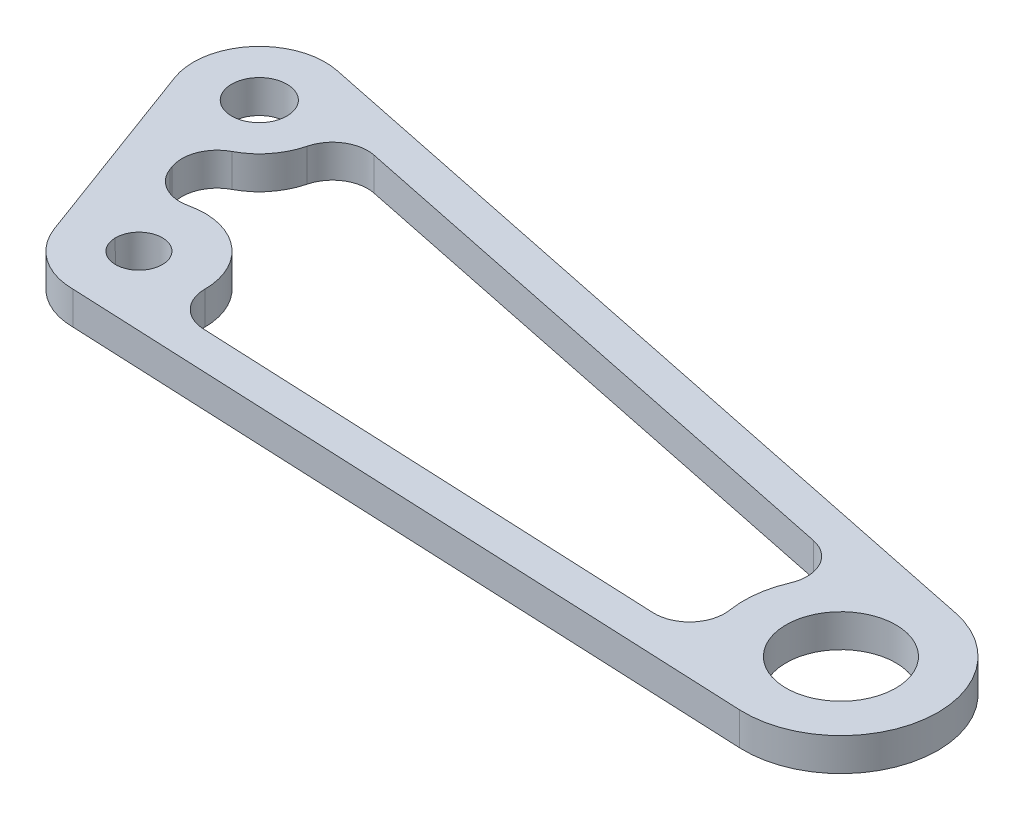
SolidWorks part; units mm, degrees
material "6061-T6 (SS)"
ref_plane "Front Plane" through (0, 0, 0) normal (0, 0, 1) x (1, 0, 0)
ref_plane "Top Plane" through (0, 0, 0) normal (0, 1, 0) x (1, 0, 0)
ref_plane "Right Plane" through (0, 0, 0) normal (1, 0, 0) x (0, 0, -1)
sketch "Sketch1" plane through (0, 0, 0) normal (0, 1, 0) x (1, 0, 0)
  line L0 (0, 0) -> (101.5644, 0) construction
  line L1 (101.5644, 0) -> (-10.2264, 27.6351) construction
  line L2 (-10.2264, 27.6351) -> (0, 0) construction
  line L3 (-23.321, 35.5752) -> (-8.933, -3.3057)
  line L8 (-8.3044, 36.9641) -> (104.3962, 13.7448)
  line L9 (0, -9.525) -> (100.9402, -14.0196)
  circle A0 centre (0, 0) radius 3.3782
  circle A1 centre (-10.2264, 27.6351) radius 4
  circle A2 centre (101.5644, 0) radius 7.9375
  arc A6 (154.4744, -3.2678) -> (153.7124, -9.525) centre (153.7124, -6.35) cw
  arc A8 (-19.5814, 39.7594) -> (-23.321, 35.5752) centre (-20.3433, 36.6771) ccw
  circle A9 centre (101.5644, 0) radius 14.0335
  circle A10 centre (0, 0) radius 9.525
  circle A11 centre (-10.2264, 27.6351) radius 9.525
  dimension "D4" = 15.875
  dimension "D5" = 8
  dimension "D6" = 9.525
  dimension "D9" = 6.7564
  dimension "D10" = 6.096
  dimension "D7" = 6.1468
  dimension "D8" = 5.525
  dimension "D2" = 29.4665
  dimension "D3" = 115.156
  dimension "D13" = 101.5644
extrude "Boss-Extrude2" add sketch "Sketch1" along normal blind 4.7625 contours A11 L3 A10 A9 | A10 A0 | A9 A2 | A11 A1 region at (40.933, 0, -8.4018) region at (-17.2469, 0, -33.6666) region at (-1.6316, 0, -9.1106) region at (112.1352, 0, -8.6149)
sketch "Sketch2" plane through (0, 4.7625, 0) normal (0, 1, 0) x (1, 0, 0)
  line L0 (-10.2264, 27.6351) -> (101.5644, 0)
  line L1 (101.5644, 0) -> (0, 0)
  line L2 (0, 0) -> (-10.2264, 27.6351)
  line L3 (-1.0786, 30.2887) -> (92.7872, 10.9499)
  line L4 (8.2235, -4.8061) -> (90.3707, -8.4639)
  line L5 (-16.3207, 34.9553) -> (0.139, -9.524)
  line L6 (-19.1594, 24.3294) -> (-8.933, -3.3057) construction
  line L7 (-8.3044, 36.9641) -> (104.3962, 13.7448) construction
  line L8 (0, -9.525) -> (100.9402, -14.0196) construction
  line L9 (-1.2935, 30.9407) -> (11.997, -4.9742)
  circle A0 centre (-10.2264, 27.6351) radius 9.525
  circle A1 centre (0, 0) radius 9.525
  circle A2 centre (101.5644, 0) radius 14.0335
  circle A4 centre (101.5644, 0) radius 7.9375 construction
  arc A5 (100.9402, -14.0196) -> (104.3962, 13.7448) centre (101.5644, 0) ccw construction
  arc A6 (-8.3044, 36.9641) -> (-19.1594, 24.3294) centre (-10.2264, 27.6351) ccw construction
  arc A7 (-8.933, -3.3057) -> (0, -9.525) centre (0, 0) ccw construction
  dimension "D1" = 6.35
  dimension "D2" = 5.08
  dimension "D3" = 5.08
extrude "Cut-Extrude1" cut sketch "Sketch2" against normal through all contours A2 L0 L9 A1 L1 | A2 L3 L9 L0 | A2 L1 A1 L4 | A1 L9 L0 A0 L2 | A0 L0 L9 L3 | A1 L1 L9 | A1 L4 L9 L1 | A1 L2 A0 L5 region at (-0.2166, 4.7625, -26.5844) region at (0.0572, 4.7625, -15.4252) region at (-6.627, 4.7625, -13.2574) region at (48.9758, 4.7625, -16.5434) region at (36.3839, 4.7625, -8.4441) region at (9.6562, 4.7625, -0.8369) region at (53.0895, 4.7625, 3.426) region at (10.1245, 4.7625, 3.0934)
fillet "Fillet1" radius 5.08 6 edges at (-10.0875, 2.3813, -18.1111) (-6.0943, 2.3813, -7.3202) (92.7872, 2.3813, -10.9499) (90.3707, 2.3813, 8.4639) (-1.0786, 2.3813, -30.2887) (8.2235, 2.3813, 4.8061)
ref_axis "Axis1" through (0, 4.7625, 0) along (0, -1, 0)
ref_plane "Plane1" through (0, 0, 0) normal (-0.0159, 0, -0.9999) x (0, -1, 0)
split line "Split Line1" [suppressed]
ref_point "Point2" [suppressed]
sketch "Sketch3" plane through (0, 0, 0) normal (-0.0159, 0, -0.9999) x (0, -1, 0)
  line L0 (-3.175, 28.2234) -> (-3.175, -33.0358)
  line L1 (-4.7625, -99.8174) -> (-4.7625, 15.2548) construction
  dimension "D1" = 1.5875
ref_plane "Plane2" through (-0.0012, 0.0017, -0.0731) normal (-0.0159, 0.023, -0.9996) x (0.9999, 0, -0.0159)
split line "Split Line3"
ref_point "Point4"
fillet "Fillet2" [suppressed] radius 2.54
